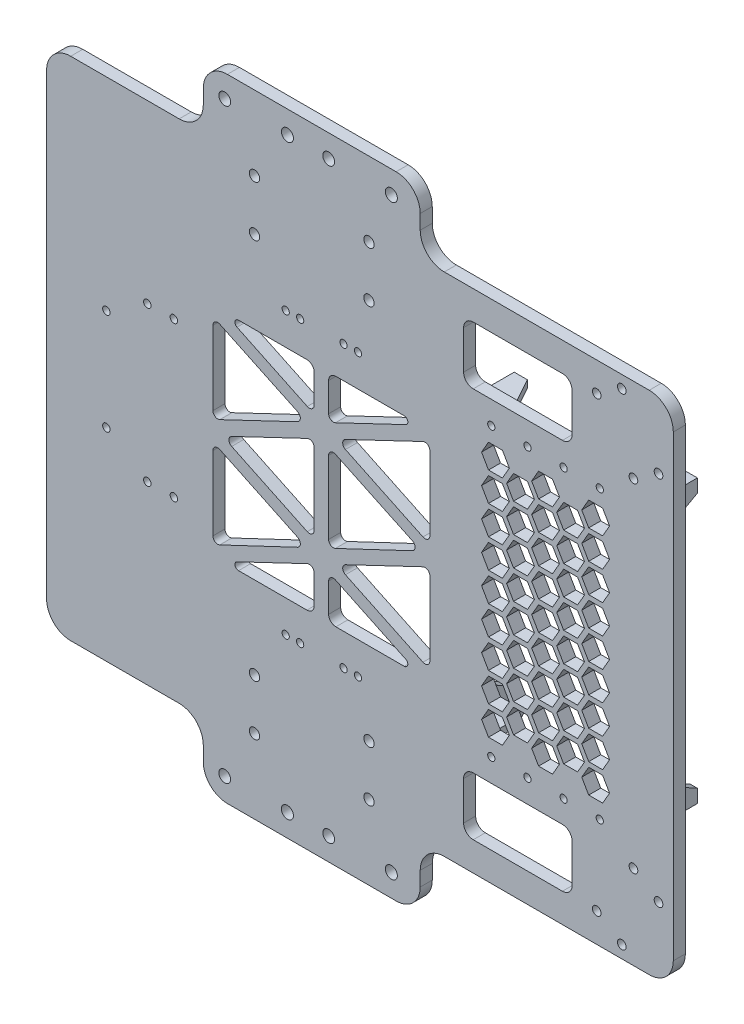
SolidWorks part; units mm, degrees
ref_plane "前视基准面" through (0, 0, 0) normal (0, 0, 1) x (1, 0, 0)
ref_plane "上视基准面" through (0, 0, 0) normal (0, 1, 0) x (1, 0, 0)
ref_plane "右视基准面" through (0, 0, 0) normal (1, 0, 0) x (0, 0, -1)
sketch "草图1" plane through (0, 0, 0) normal (0, 0, 1) x (1, 0, 0)
  line L2 (-130, 95) -> (-130, -95)
  line L3 (-120, -105) -> (-75, -105)
  line L4 (130, 95) -> (130, -95)
  line L5 (126.7518, 102.3765) -> (130, 105) construction
  line L6 (-130, -105) -> (-126.7518, -102.3765) construction
  line L9 (-65, -115) -> (-65, -121)
  line L10 (-55, -131) -> (15, -131)
  line L11 (25, -121) -> (25, -115)
  line L13 (35, -105) -> (120, -105)
  line L14 (126.7518, -102.3765) -> (130, -105) construction
  line L15 (-130, 105) -> (-126.7518, 102.3765) construction
  line L16 (-130, 0) -> (130, 0) construction
  line L17 (35, 105) -> (120, 105)
  line L18 (25, 121) -> (25, 115)
  line L19 (-55, 131) -> (15, 131)
  line L20 (-65, 115) -> (-65, 121)
  line L21 (-120, 105) -> (-75, 105)
  arc A1 (-120, -105) -> (-130, -95) centre (-120, -95) cw
  arc A3 (120, -105) -> (130, -95) centre (120, -95) ccw
  arc A8 (-65, -115) -> (-75, -105) centre (-75, -115) ccw
  arc A9 (25, -115) -> (35, -105) centre (35, -115) cw
  arc A10 (-55, -131) -> (-65, -121) centre (-55, -121) cw
  arc A11 (15, -131) -> (25, -121) centre (15, -121) ccw
  arc A12 (15, 131) -> (25, 121) centre (15, 121) cw
  arc A13 (-55, 131) -> (-65, 121) centre (-55, 121) ccw
  arc A14 (25, 115) -> (35, 105) centre (35, 115) ccw
  arc A15 (-65, 115) -> (-75, 105) centre (-75, 115) cw
  arc A16 (120, 105) -> (130, 95) centre (120, 95) cw
  arc A17 (-120, 105) -> (-130, 95) centre (-120, 95) ccw
  point P0 (0, 0)
  point P40 (25, -105)
  point P45 (25, 105)
  dimension "D2" = 10
  dimension "D3" = 65
  dimension "D4" = 10
  dimension "D5" = 105
  dimension "D7" = 10
  dimension "D8" = 10
  dimension "D10" = 10
  dimension "D12" = 10
  dimension "D13" = 105
  dimension "D18" = 90
  dimension "D19" = 6
extrude "凸台-拉伸1" add sketch "草图1" along normal blind 5
sketch "草图4" plane through (0, 0, 0) normal (0, 0, -1) x (-1, 0, 0)
  line L0 (-39, -47.5) -> (-39, -58.5)
  line L1 (-39, -58.5) -> (-50, -58.5)
  line L2 (-50, -58.5) -> (-50, -55.5)
  line L3 (-50, -55.5) -> (-42, -55.5)
  line L4 (-42, -55.5) -> (-42, -47.5)
  line L5 (-42, -47.5) -> (-39, -47.5)
  line L6 (-130, 0) -> (-25.5592, 0) construction
  line L7 (-130, -95) -> (-130, 95) construction
  line L10 (-130, -95) -> (-130, 95) construction
  dimension "D1" = 11
  dimension "D2" = 11
  dimension "D3" = 3
  dimension "D4" = 3
  dimension "D5" = 80
  dimension "D7" = 55.5
extrude "凸台-拉伸2" add sketch "草图4" along normal blind 20
sketch "草图5" plane through (0, -58.5, 0) normal (0, -1, 0) x (1, 0, 0)
  line L0 (50, -10) -> (44.5, -20)
  line L1 (50, -20) -> (50, 0) construction
  line L2 (50, -20) -> (39, -20) construction
  line L3 (44.5, -20) -> (50, -20)
  line L4 (50, -20) -> (50, -10)
  dimension "D1" = 10
  dimension "D2" = 5.5
extrude "切除-拉伸3" cut sketch "草图5" against normal blind 10
sketch "草图6" plane through (39, 0, 0) normal (-1, 0, 0) x (0, 0, 1)
  line L0 (-20, -53) -> (-10, -47.5)
  line L1 (-20, -58.5) -> (-20, -47.5) construction
  line L2 (-20, -47.5) -> (0, -47.5) construction
  line L3 (-10, -47.5) -> (-20, -47.5)
  line L4 (-20, -47.5) -> (-20, -53)
  dimension "D1" = 10
  dimension "D2" = 5.5
extrude "切除-拉伸4" cut sketch "草图6" against normal blind 10
ref_plane "基准面2" through (77, 0, 0) normal (1, 0, 0) x (0, 0, -1)
mirror "镜向1" about plane through (77, 0, 0) normal (1, 0, 0) of "凸台-拉伸2", "切除-拉伸4", "切除-拉伸3"
mirror "镜向2" about plane through (0, 0, 0) normal (0, 1, 0) of "镜向1"
sketch "草图7" plane through (0, 0, 0) normal (0, 0, -1) x (-1, 0, 0)
  line L4 (-112, -55.5) -> (-104, -55.5) construction
  line L5 (-112, 47.5) -> (-112, 55.5) construction
  line L6 (-112, 55.5) -> (-104, 55.5) construction
  line L7 (-92.013, 36) -> (-94.8997, 41)
  line L8 (-94.8997, 41) -> (-100.6732, 41)
  line L9 (-100.6732, 41) -> (-103.56, 36)
  line L10 (-103.56, 36) -> (-100.6732, 31)
  line L11 (-100.6732, 31) -> (-94.8997, 31)
  line L12 (-94.8997, 31) -> (-92.013, 36)
  line L13 (-77.0019, 36) -> (-97.7865, 36) construction
  line L14 (-74.1151, 31) -> (-71.2284, 36)
  line L15 (-71.2284, 36) -> (-74.1151, 41)
  line L16 (-74.1151, 41) -> (-79.8886, 41)
  line L17 (-79.8886, 41) -> (-82.7754, 36)
  line L18 (-82.7754, 36) -> (-79.8886, 31)
  line L19 (-79.8886, 31) -> (-74.1151, 31)
  line L20 (-92.013, 24) -> (-94.8997, 29)
  line L21 (-93.1677, 30) -> (-90.2809, 25)
  line L22 (-90.2809, 25) -> (-84.5074, 25)
  line L23 (-84.5074, 25) -> (-81.6207, 30)
  line L24 (-81.6207, 30) -> (-84.5074, 35)
  line L25 (-84.5074, 35) -> (-90.2809, 35)
  line L26 (-90.2809, 35) -> (-93.1677, 30)
  line L27 (-84.5074, 37) -> (-81.6207, 42)
  line L28 (-81.6207, 42) -> (-84.5074, 47)
  line L29 (-84.5074, 47) -> (-90.2809, 47)
  line L30 (-90.2809, 47) -> (-93.1677, 42)
  line L31 (-93.1677, 42) -> (-90.2809, 37)
  line L32 (-90.2809, 37) -> (-84.5074, 37)
  line L33 (-79.8886, 43) -> (-74.1151, 43)
  line L34 (-74.1151, 43) -> (-71.2284, 48)
  line L35 (-71.2284, 48) -> (-74.1151, 53)
  line L36 (-74.1151, 53) -> (-79.8886, 53)
  line L37 (-79.8886, 53) -> (-82.7754, 48)
  line L38 (-82.7754, 48) -> (-79.8886, 43)
  line L39 (-94.8997, 43) -> (-92.013, 48)
  line L40 (-92.013, 48) -> (-94.8997, 53)
  line L41 (-94.8997, 53) -> (-100.6732, 53)
  line L42 (-100.6732, 53) -> (-103.56, 48)
  line L43 (-103.56, 48) -> (-100.6732, 43)
  line L44 (-100.6732, 43) -> (-94.8997, 43)
  line L45 (-72.3831, 42) -> (-69.4963, 37)
  line L46 (-69.4963, 37) -> (-63.7228, 37)
  line L47 (-63.7228, 37) -> (-60.8361, 42)
  line L48 (-60.8361, 42) -> (-63.7228, 47)
  line L49 (-63.7228, 47) -> (-69.4963, 47)
  line L50 (-69.4963, 47) -> (-72.3831, 42)
  line L51 (-94.8997, 29) -> (-100.6732, 29)
  line L52 (-100.6732, 29) -> (-103.56, 24)
  line L53 (-103.56, 24) -> (-100.6732, 19)
  line L54 (-100.6732, 19) -> (-94.8997, 19)
  line L55 (-94.8997, 19) -> (-92.013, 24)
  line L56 (-93.1677, 18) -> (-90.2809, 13)
  line L57 (-90.2809, 13) -> (-84.5074, 13)
  line L58 (-84.5074, 13) -> (-81.6207, 18)
  line L59 (-81.6207, 18) -> (-84.5074, 23)
  line L60 (-84.5074, 23) -> (-90.2809, 23)
  line L61 (-90.2809, 23) -> (-93.1677, 18)
  line L62 (-74.1151, 19) -> (-71.2284, 24)
  line L63 (-71.2284, 24) -> (-74.1151, 29)
  line L64 (-74.1151, 29) -> (-79.8886, 29)
  line L65 (-79.8886, 29) -> (-82.7754, 24)
  line L66 (-82.7754, 24) -> (-79.8886, 19)
  line L67 (-79.8886, 19) -> (-74.1151, 19)
  line L68 (-72.3831, 30) -> (-69.4963, 25)
  line L69 (-69.4963, 25) -> (-63.7228, 25)
  line L70 (-63.7228, 25) -> (-60.8361, 30)
  line L71 (-60.8361, 30) -> (-63.7228, 35)
  line L72 (-63.7228, 35) -> (-69.4963, 35)
  line L73 (-69.4963, 35) -> (-72.3831, 30)
  line L74 (-92.013, 12) -> (-94.8997, 17)
  line L75 (-94.8997, 17) -> (-100.6732, 17)
  line L76 (-100.6732, 17) -> (-103.56, 12)
  line L77 (-103.56, 12) -> (-100.6732, 7)
  line L78 (-100.6732, 7) -> (-94.8997, 7)
  line L79 (-94.8997, 7) -> (-92.013, 12)
  line L80 (-93.1677, 6) -> (-90.2809, 1)
  line L81 (-90.2809, 1) -> (-84.5074, 1)
  line L82 (-84.5074, 1) -> (-81.6207, 6)
  line L83 (-81.6207, 6) -> (-84.5074, 11)
  line L84 (-84.5074, 11) -> (-90.2809, 11)
  line L85 (-90.2809, 11) -> (-93.1677, 6)
  line L86 (-74.1151, 7) -> (-71.2284, 12)
  line L87 (-71.2284, 12) -> (-74.1151, 17)
  line L88 (-74.1151, 17) -> (-79.8886, 17)
  line L89 (-79.8886, 17) -> (-82.7754, 12)
  line L90 (-82.7754, 12) -> (-79.8886, 7)
  line L91 (-79.8886, 7) -> (-74.1151, 7)
  line L92 (-72.3831, 18) -> (-69.4963, 13)
  line L93 (-69.4963, 13) -> (-63.7228, 13)
  line L94 (-63.7228, 13) -> (-60.8361, 18)
  line L95 (-60.8361, 18) -> (-63.7228, 23)
  line L96 (-63.7228, 23) -> (-69.4963, 23)
  line L97 (-69.4963, 23) -> (-72.3831, 18)
  line L98 (-92.013, 0) -> (-94.8997, 5)
  line L99 (-94.8997, 5) -> (-100.6732, 5)
  line L100 (-100.6732, 5) -> (-103.56, 0)
  line L101 (-103.56, 0) -> (-100.6732, -5)
  line L102 (-100.6732, -5) -> (-94.8997, -5)
  line L103 (-94.8997, -5) -> (-92.013, 0)
  line L104 (-93.1677, -6) -> (-90.2809, -11)
  line L105 (-90.2809, -11) -> (-84.5074, -11)
  line L106 (-84.5074, -11) -> (-81.6207, -6)
  line L107 (-81.6207, -6) -> (-84.5074, -1)
  line L108 (-84.5074, -1) -> (-90.2809, -1)
  line L109 (-90.2809, -1) -> (-93.1677, -6)
  line L110 (-74.1151, -5) -> (-71.2284, 0)
  line L111 (-71.2284, 0) -> (-74.1151, 5)
  line L112 (-74.1151, 5) -> (-79.8886, 5)
  line L113 (-79.8886, 5) -> (-82.7754, 0)
  line L114 (-82.7754, 0) -> (-79.8886, -5)
  line L115 (-79.8886, -5) -> (-74.1151, -5)
  line L116 (-72.3831, 6) -> (-69.4963, 1)
  line L117 (-69.4963, 1) -> (-63.7228, 1)
  line L118 (-63.7228, 1) -> (-60.8361, 6)
  line L119 (-60.8361, 6) -> (-63.7228, 11)
  line L120 (-63.7228, 11) -> (-69.4963, 11)
  line L121 (-69.4963, 11) -> (-72.3831, 6)
  line L122 (-92.013, -12) -> (-94.8997, -7)
  line L123 (-94.8997, -7) -> (-100.6732, -7)
  line L124 (-100.6732, -7) -> (-103.56, -12)
  line L125 (-103.56, -12) -> (-100.6732, -17)
  line L126 (-100.6732, -17) -> (-94.8997, -17)
  line L127 (-94.8997, -17) -> (-92.013, -12)
  line L128 (-93.1677, -18) -> (-90.2809, -23)
  line L129 (-90.2809, -23) -> (-84.5074, -23)
  line L130 (-84.5074, -23) -> (-81.6207, -18)
  line L131 (-81.6207, -18) -> (-84.5074, -13)
  line L132 (-84.5074, -13) -> (-90.2809, -13)
  line L133 (-90.2809, -13) -> (-93.1677, -18)
  line L134 (-74.1151, -17) -> (-71.2284, -12)
  line L135 (-71.2284, -12) -> (-74.1151, -7)
  line L136 (-74.1151, -7) -> (-79.8886, -7)
  line L137 (-79.8886, -7) -> (-82.7754, -12)
  line L138 (-82.7754, -12) -> (-79.8886, -17)
  line L139 (-79.8886, -17) -> (-74.1151, -17)
  line L140 (-72.3831, -6) -> (-69.4963, -11)
  line L141 (-69.4963, -11) -> (-63.7228, -11)
  line L142 (-63.7228, -11) -> (-60.8361, -6)
  line L143 (-60.8361, -6) -> (-63.7228, -1)
  line L144 (-63.7228, -1) -> (-69.4963, -1)
  line L145 (-69.4963, -1) -> (-72.3831, -6)
  line L146 (-92.013, -24) -> (-94.8997, -19)
  line L147 (-94.8997, -19) -> (-100.6732, -19)
  line L148 (-100.6732, -19) -> (-103.56, -24)
  line L149 (-103.56, -24) -> (-100.6732, -29)
  line L150 (-100.6732, -29) -> (-94.8997, -29)
  line L151 (-94.8997, -29) -> (-92.013, -24)
  line L152 (-93.1677, -30) -> (-90.2809, -35)
  line L153 (-90.2809, -35) -> (-84.5074, -35)
  line L154 (-84.5074, -35) -> (-81.6207, -30)
  line L155 (-81.6207, -30) -> (-84.5074, -25)
  line L156 (-84.5074, -25) -> (-90.2809, -25)
  line L157 (-90.2809, -25) -> (-93.1677, -30)
  line L158 (-74.1151, -29) -> (-71.2284, -24)
  line L159 (-71.2284, -24) -> (-74.1151, -19)
  line L160 (-74.1151, -19) -> (-79.8886, -19)
  line L161 (-79.8886, -19) -> (-82.7754, -24)
  line L162 (-82.7754, -24) -> (-79.8886, -29)
  line L163 (-79.8886, -29) -> (-74.1151, -29)
  line L164 (-72.3831, -18) -> (-69.4963, -23)
  line L165 (-69.4963, -23) -> (-63.7228, -23)
  line L166 (-63.7228, -23) -> (-60.8361, -18)
  line L167 (-60.8361, -18) -> (-63.7228, -13)
  line L168 (-63.7228, -13) -> (-69.4963, -13)
  line L169 (-69.4963, -13) -> (-72.3831, -18)
  line L170 (-92.013, -36) -> (-94.8997, -31)
  line L171 (-94.8997, -31) -> (-100.6732, -31)
  line L172 (-100.6732, -31) -> (-103.56, -36)
  line L173 (-103.56, -36) -> (-100.6732, -41)
  line L174 (-100.6732, -41) -> (-94.8997, -41)
  line L175 (-94.8997, -41) -> (-92.013, -36)
  line L176 (-93.1677, -42) -> (-90.2809, -47)
  line L177 (-90.2809, -47) -> (-84.5074, -47)
  line L178 (-84.5074, -47) -> (-81.6207, -42)
  line L179 (-81.6207, -42) -> (-84.5074, -37)
  line L180 (-84.5074, -37) -> (-90.2809, -37)
  line L181 (-90.2809, -37) -> (-93.1677, -42)
  line L182 (-74.1151, -41) -> (-71.2284, -36)
  line L183 (-71.2284, -36) -> (-74.1151, -31)
  line L184 (-74.1151, -31) -> (-79.8886, -31)
  line L185 (-79.8886, -31) -> (-82.7754, -36)
  line L186 (-82.7754, -36) -> (-79.8886, -41)
  line L187 (-79.8886, -41) -> (-74.1151, -41)
  line L188 (-72.3831, -30) -> (-69.4963, -35)
  line L189 (-69.4963, -35) -> (-63.7228, -35)
  line L190 (-63.7228, -35) -> (-60.8361, -30)
  line L191 (-60.8361, -30) -> (-63.7228, -25)
  line L192 (-63.7228, -25) -> (-69.4963, -25)
  line L193 (-69.4963, -25) -> (-72.3831, -30)
  line L194 (-92.013, -48) -> (-94.8997, -43)
  line L195 (-94.8997, -43) -> (-100.6732, -43)
  line L196 (-100.6732, -43) -> (-103.56, -48)
  line L197 (-103.56, -48) -> (-100.6732, -53)
  line L198 (-100.6732, -53) -> (-94.8997, -53)
  line L199 (-94.8997, -53) -> (-92.013, -48)
  line L206 (-74.1151, -53) -> (-71.2284, -48)
  line L207 (-71.2284, -48) -> (-74.1151, -43)
  line L208 (-74.1151, -43) -> (-79.8886, -43)
  line L209 (-79.8886, -43) -> (-82.7754, -48)
  line L210 (-82.7754, -48) -> (-79.8886, -53)
  line L211 (-79.8886, -53) -> (-74.1151, -53)
  line L212 (-72.3831, -42) -> (-69.4963, -47)
  line L213 (-69.4963, -47) -> (-63.7228, -47)
  line L214 (-63.7228, -47) -> (-60.8361, -42)
  line L215 (-60.8361, -42) -> (-63.7228, -37)
  line L216 (-63.7228, -37) -> (-69.4963, -37)
  line L217 (-69.4963, -37) -> (-72.3831, -42)
  line L218 (-61.9908, 36) -> (-59.104, 31)
  line L219 (-61.9908, 48) -> (-59.104, 43)
  line L220 (-59.104, 43) -> (-53.3305, 43)
  line L221 (-53.3305, 43) -> (-50.4438, 48)
  line L222 (-50.4438, 48) -> (-53.3305, 53)
  line L223 (-53.3305, 53) -> (-59.104, 53)
  line L224 (-59.104, 53) -> (-61.9908, 48)
  line L225 (-59.104, 31) -> (-53.3305, 31)
  line L226 (-53.3305, 31) -> (-50.4438, 36)
  line L227 (-50.4438, 36) -> (-53.3305, 41)
  line L228 (-53.3305, 41) -> (-59.104, 41)
  line L229 (-59.104, 41) -> (-61.9908, 36)
  line L230 (-61.9908, 24) -> (-59.104, 19)
  line L231 (-59.104, 19) -> (-53.3305, 19)
  line L232 (-53.3305, 19) -> (-50.4438, 24)
  line L233 (-50.4438, 24) -> (-53.3305, 29)
  line L234 (-53.3305, 29) -> (-59.104, 29)
  line L235 (-59.104, 29) -> (-61.9908, 24)
  line L236 (-61.9908, 12) -> (-59.104, 7)
  line L237 (-59.104, 7) -> (-53.3305, 7)
  line L238 (-53.3305, 7) -> (-50.4438, 12)
  line L239 (-50.4438, 12) -> (-53.3305, 17)
  line L240 (-53.3305, 17) -> (-59.104, 17)
  line L241 (-59.104, 17) -> (-61.9908, 12)
  line L242 (-61.9908, 0) -> (-59.104, -5)
  line L243 (-59.104, -5) -> (-53.3305, -5)
  line L244 (-53.3305, -5) -> (-50.4438, 0)
  line L245 (-50.4438, 0) -> (-53.3305, 5)
  line L246 (-53.3305, 5) -> (-59.104, 5)
  line L247 (-59.104, 5) -> (-61.9908, 0)
  line L248 (-61.9908, -12) -> (-59.104, -17)
  line L249 (-59.104, -17) -> (-53.3305, -17)
  line L250 (-53.3305, -17) -> (-50.4438, -12)
  line L251 (-50.4438, -12) -> (-53.3305, -7)
  line L252 (-53.3305, -7) -> (-59.104, -7)
  line L253 (-59.104, -7) -> (-61.9908, -12)
  line L254 (-61.9908, -24) -> (-59.104, -29)
  line L255 (-59.104, -29) -> (-53.3305, -29)
  line L256 (-53.3305, -29) -> (-50.4438, -24)
  line L257 (-50.4438, -24) -> (-53.3305, -19)
  line L258 (-53.3305, -19) -> (-59.104, -19)
  line L259 (-59.104, -19) -> (-61.9908, -24)
  line L260 (-61.9908, -36) -> (-59.104, -41)
  line L261 (-59.104, -41) -> (-53.3305, -41)
  line L262 (-53.3305, -41) -> (-50.4438, -36)
  line L263 (-50.4438, -36) -> (-53.3305, -31)
  line L264 (-53.3305, -31) -> (-59.104, -31)
  line L265 (-59.104, -31) -> (-61.9908, -36)
  line L266 (-61.9908, -48) -> (-59.104, -53)
  line L267 (-59.104, -53) -> (-53.3305, -53)
  line L268 (-53.3305, -53) -> (-50.4438, -48)
  line L269 (-50.4438, -48) -> (-53.3305, -43)
  line L270 (-53.3305, -43) -> (-59.104, -43)
  line L271 (-59.104, -43) -> (-61.9908, -48)
  line L272 (-93.1677, -54) -> (-90.2809, -59) [skipped]
  line L273 (-90.2809, -59) -> (-84.5074, -59) [skipped]
  line L274 (-84.5074, -59) -> (-81.6207, -54) [skipped]
  line L275 (-81.6207, -54) -> (-84.5074, -49) [skipped]
  line L276 (-84.5074, -49) -> (-90.2809, -49) [skipped]
  line L277 (-90.2809, -49) -> (-93.1677, -54) [skipped]
  circle A0 centre (-97.7865, 36) radius 5 construction
  circle A1 centre (-77.0019, 36) radius 5 construction
  circle A2 centre (-87.3942, 30) radius 5 construction
  circle A3 centre (-87.3942, 42) radius 5 construction
  circle A4 centre (-77.0019, 48) radius 5 construction
  circle A5 centre (-97.7865, 48) radius 5 construction
  circle A6 centre (-66.6096, 42) radius 5 construction
  circle A7 centre (-56.2173, 48) radius 5 construction
  point P4 (-87.3942, 37)
  dimension "D1" = 2
  dimension "D3" = 10
  dimension "D4" = 10
  dimension "D5" = 2
  dimension "D7" = 10
  dimension "D11" = 10
  dimension "D14" = 10
  dimension "D15" = 10
  dimension "D20" = 10
  dimension "D2" = 2
  dimension "D6" = 2
  dimension "D8" = 2
  dimension "D9" = 2
  dimension "D10" = 2
  dimension "D12" = 2
  dimension "D13" = 2
  dimension "D16" = 2
  dimension "D17" = 2
  dimension "D19" = 2
  dimension "D21" = 9
  dimension "D22" = 2.5
  dimension "D23" = 2.5
  dimension "D24" = 8.44
  dimension "D18" = 8
extrude "切除-拉伸5" cut sketch "草图7" against normal blind 5
sketch "草图8" plane through (0, 0, 0) normal (0, 0, -1) x (-1, 0, 0)
  line L0 (-75.3677, 120) -> (-75.3677, -120)
  line L1 (-100.0285, 77.2863) -> (-100.0285, -77.2863)
  line L2 (-100.0285, 77.2863) -> (-75.3677, 120)
  line L3 (-100.0285, -77.2863) -> (-75.3677, -120)
  line L4 (-37.1297, 0) -> (-146.8562, 0) construction
  dimension "D1" = 30
  dimension "D2" = 30
  dimension "D3" = 120
  dimension "D4" = 120
sketch "草图9" plane through (0, 0, 0) normal (0, 0, -1) x (-1, 0, 0)
  line L0 (148.8518, 0) -> (-37.1297, 0) construction
  line L1 (-29, 41) -> (-29, 4)
  line L2 (-25, -45) -> (13, -45)
  line L3 (61, -41) -> (61, -4)
  line L4 (57, 45) -> (19, 45)
  line L14 (-29, 41) -> (9.8049, 22.5)
  line L15 (57, 0) -> (19, -18.1163)
  line L16 (130, 95) -> (130, -95) construction
  line L17 (63, 93) -> (118, 93)
  line L18 (63, 93) -> (63, 66)
  line L19 (63, 66) -> (118, 66)
  line L20 (118, 93) -> (118, 66)
  line L21 (75, 105) -> (120, 105) construction
  line L22 (63, -66) -> (118, -66)
  line L23 (118, -93) -> (118, -66)
  line L24 (63, -93) -> (118, -93)
  line L25 (63, -93) -> (63, -66)
  line L26 (-120, 105) -> (-35, 105) construction
  line L27 (-43, 93) -> (-88, 93)
  line L28 (-43, 93) -> (-43, 69)
  line L29 (-43, 69) -> (-88, 69)
  line L30 (-88, 93) -> (-88, 69)
  line L31 (-130, -95) -> (-130, 95) construction
  line L32 (-43, -69) -> (-88, -69)
  line L33 (-88, -93) -> (-88, -69)
  line L34 (-43, -93) -> (-88, -93)
  line L35 (-43, -93) -> (-43, -69)
  line L36 (-25, 45) -> (13, 26.8837)
  line L37 (-25, -45) -> (13, -26.8837)
  line L38 (61, 41) -> (22.0746, 22.5575)
  line L39 (-25.5359, 0) -> (13, -18.258)
  line L40 (57, 45) -> (19, 26.8837)
  line L41 (57, -45) -> (19, -26.8837)
  line L42 (16, 61.4977) -> (16, -60.5731) construction
  line L43 (13, 45) -> (13, 26.8837)
  line L44 (19, 45) -> (19, 26.8837)
  line L45 (13, 18.258) -> (13, -18.258)
  line L46 (9.8049, 22.5) -> (-29, 4)
  line L47 (19, 18.1163) -> (57, 0)
  line L48 (22.0746, 22.5575) -> (61, 4)
  line L49 (13, 18.258) -> (-25.5359, 0)
  line L50 (19, 18.1163) -> (19, -18.1163)
  line L51 (22.0746, -22.5575) -> (61, -41)
  line L52 (9.8049, -22.5) -> (-29, -41)
  line L53 (9.8049, -22.5) -> (-29, -4)
  line L54 (22.0746, -22.5575) -> (61, -4)
  line L55 (13, -26.8837) -> (13, -45)
  line L56 (19, -26.8837) -> (19, -45)
  line L57 (13, 45) -> (-25, 45)
  line L58 (-29, -4) -> (-29, -41)
  line L59 (19, -45) -> (57, -45)
  line L60 (61, 4) -> (61, 41)
  line L61 (-44, 41) -> (-44, -37.8122) construction
  dimension "D1" = 45
  dimension "D2" = 45
  dimension "D3" = 15
  dimension "D4" = 90
  dimension "D5" = 1
  dimension "D7" = 12
  dimension "D8" = 12
  dimension "D9" = 27
  dimension "D10" = 55
  dimension "D11" = 12
  dimension "D12" = 45
  dimension "D13" = 42
  dimension "D14" = 24
  dimension "D21" = 4
  dimension "D22" = 4
  dimension "D23" = 4
  dimension "D24" = 4
  dimension "D26" = 4
  dimension "D27" = 3
  dimension "D28" = 45
extrude "切除-拉伸6" cut sketch "草图9" against normal blind 5 contours L27 L30 L29 L28 | L34 L35 L32 L33 | L4 L44 L40 | L48 L60 L38 | L47 L50 L15 | L54 L51 L3 | L56 L59 L41 | L55 L37 L2 | L53 L58 L52 | L45 L49 L39 | L46 L14 L1 | L43 L57 L36 | L57 L36 L43 region at (16.065, 22.5, 0) region at (-0.3333, -38.9612, 0) region at (-48.0249, -22.5192, 0) region at (-31.6667, 38.9612, 0) region at (-31.6667, 0, 0) region at (65.5, 81, 0) region at (65.5, -81, 0) region at (-0.3333, 38.9612, 0) region at (-48.0249, 22.5192, 0) region at (-0.1547, 0, 0) region at (-31.6667, -38.9612, 0) region at (16.065, -22.5, 0)
fillet "圆角1" radius 4 8 edges at (43, -93, 2.5) (88, -69, 2.5) (43, -69, 2.5) (88, -93, 2.5) (88, 69, 2.5) (43, 69, 2.5) (43, 93, 2.5) (88, 93, 2.5)
fillet "圆角2" radius 1.5 4 edges at (25, -45, 2.5) (-57, -45, 2.5) (25, 45, 2.5) (-57, 45, 2.5)
fillet "圆角3" radius 2 22 edges at (29, -4, 2.5) (29, 4, 2.5) (-13, -18.258, 2.5) (-61, -41, 2.5) (-61, 4, 2.5) (-13, -26.8837, 2.5) (-13, 18.258, 2.5) (-61, -4, 2.5) (-22.0746, -22.5575, 2.5) (25.5359, 0, 2.5) (-22.0746, 22.5575, 2.5) (-61, 41, 2.5) (-19, 26.8837, 2.5) (-19, -26.8837, 2.5) (-19, -18.1163, 2.5) (29, -41, 2.5) (29, 41, 2.5) (-57, 0, 2.5) (-9.8049, -22.5, 2.5) (-13, 26.8837, 2.5) (-9.8049, 22.5, 2.5) (-19, 18.1163, 2.5)
fillet "圆角4" radius 3 4 edges at (-13, -45, 2.5) (-13, 45, 2.5) (-19, -45, 2.5) (-19, 45, 2.5)
sketch "草图10" plane through (0, 0, 0) normal (0, 0, -1) x (-1, 0, 0)
  line L0 (-37.1297, 0) -> (-146.8562, 0) construction
  line L1 (-37.1297, 0) -> (-146.8562, 0) construction
  circle A0 centre (-123.8743, 76.9597) radius 1.8 construction
  circle A1 centre (-113.4687, 70.0334) radius 1.8 construction
  circle A2 centre (-108.6364, 99.852) radius 1.8 construction
  circle A3 centre (-98.2308, 92.9256) radius 1.8 construction
  circle A4 centre (105.2101, 21) radius 1.55 construction
  circle A5 centre (88.2101, 32) radius 1.55 construction
  circle A6 centre (77.2101, 32) radius 1.55 construction
  circle A11 centre (-13.0267, 121.679) radius 2.5 construction
  circle A12 centre (56.0941, 121.679) radius 2.45 construction
  circle A13 centre (30.0941, 121.679) radius 2.5 construction
  circle A14 centre (12.9733, 121.679) radius 2.45 construction
  circle A15 centre (-123.8743, 76.9597) radius 1.8
  circle A16 centre (-113.4687, 70.0334) radius 1.8
  circle A17 centre (-108.6364, 99.852) radius 1.8
  circle A18 centre (-98.2308, 92.9256) radius 1.8
  circle A19 centre (105.2101, 21) radius 1.55
  circle A20 centre (88.2101, 32) radius 1.55
  circle A21 centre (77.2101, 32) radius 1.55
  circle A26 centre (-13.0267, 121.679) radius 2.5
  circle A27 centre (56.0941, 121.679) radius 2.45
  circle A28 centre (30.0941, 121.679) radius 2.5
  circle A29 centre (12.9733, 121.679) radius 2.45
  circle A30 centre (12.9733, -121.679) radius 2.45
  circle A31 centre (30.0941, -121.679) radius 2.5
  circle A32 centre (56.0941, -121.679) radius 2.45
  circle A33 centre (-13.0267, -121.679) radius 2.5
  circle A38 centre (77.2101, -32) radius 1.55
  circle A39 centre (88.2101, -32) radius 1.55
  circle A40 centre (105.2101, -21) radius 1.55
  circle A41 centre (-98.2308, -92.9256) radius 1.8
  circle A42 centre (-108.6364, -99.852) radius 1.8
  circle A43 centre (-113.4687, -70.0334) radius 1.8
  circle A44 centre (-123.8743, -76.9597) radius 1.8
  circle A45 centre (-99.5, 59.5) radius 1.5 construction
  circle A46 centre (-84.5, 59.5) radius 1.5 construction
  circle A47 centre (-69.5, 59.5) radius 1.5 construction
  circle A48 centre (-54.5, 59.5) radius 1.5 construction
  circle A49 centre (0.8061, 58.25) radius 1.5 construction
  circle A50 centre (6.8061, 58.25) radius 1.5 construction
  circle A51 centre (24.8061, 58.25) radius 1.5 construction
  circle A52 centre (30.8061, 58.25) radius 1.5 construction
  circle A53 centre (-99.5, 59.5) radius 1.5
  circle A54 centre (-84.5, 59.5) radius 1.5
  circle A55 centre (-69.5, 59.5) radius 1.5
  circle A56 centre (-54.5, 59.5) radius 1.5
  circle A57 centre (0.8061, 58.25) radius 1.5
  circle A58 centre (6.8061, 58.25) radius 1.5
  circle A59 centre (24.8061, 58.25) radius 1.5
  circle A60 centre (30.8061, 58.25) radius 1.5
  circle A61 centre (30.8061, -58.25) radius 1.5
  circle A62 centre (24.8061, -58.25) radius 1.5
  circle A63 centre (6.8061, -58.25) radius 1.5
  circle A64 centre (0.8061, -58.25) radius 1.5
  circle A65 centre (-54.5, -59.5) radius 1.5
  circle A66 centre (-69.5, -59.5) radius 1.5
  circle A67 centre (-84.5, -59.5) radius 1.5
  circle A68 centre (-99.5, -59.5) radius 1.5
  circle A69 centre (-3.75, 79.1665) radius 2.15 construction
  circle A70 centre (43.75, 79.1665) radius 2.15 construction
  circle A71 centre (43.75, 100.1665) radius 2.15 construction
  circle A72 centre (-3.75, 100.1665) radius 2.15 construction
  circle A73 centre (-3.75, 79.1665) radius 2.15
  circle A74 centre (43.75, 79.1665) radius 2.15
  circle A75 centre (43.75, 100.1665) radius 2.15
  circle A76 centre (-3.75, 100.1665) radius 2.15
  circle A77 centre (-3.75, -100.1665) radius 2.15
  circle A78 centre (43.75, -100.1665) radius 2.15
  circle A79 centre (43.75, -79.1665) radius 2.15
  circle A80 centre (-3.75, -79.1665) radius 2.15
  point P117 (-13.75, -77)
  point P118 (33.75, 102)
extrude "切除-拉伸7" cut sketch "草图10" against normal through all
equation "\"45、\"=43.7672"
